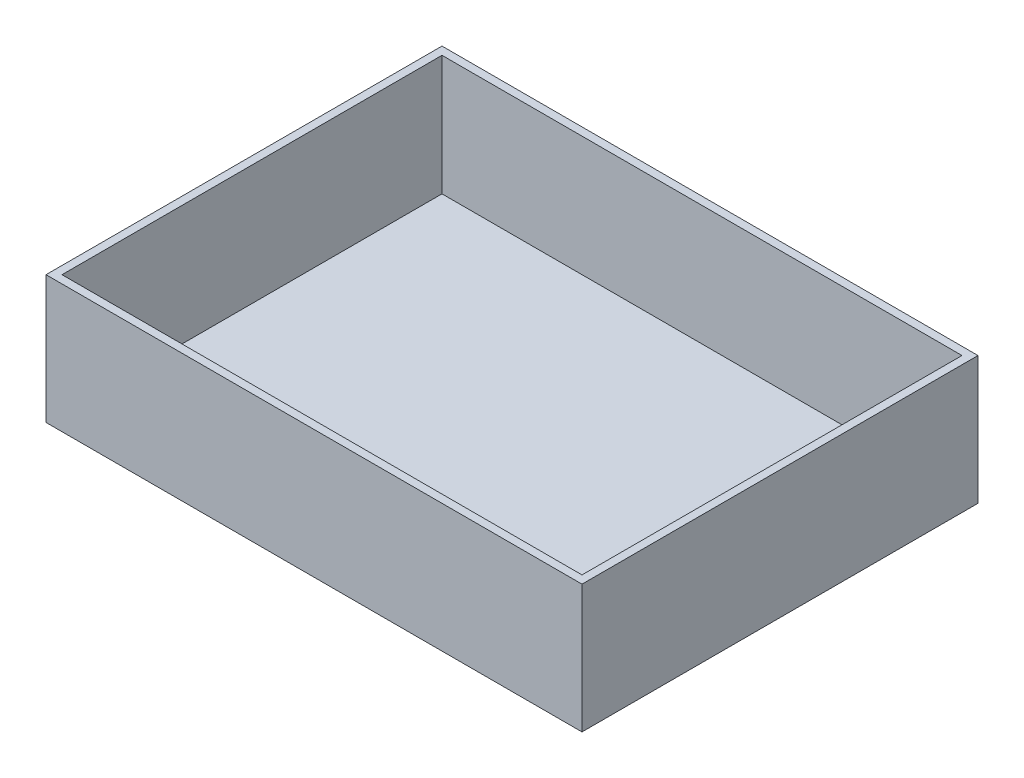
SolidWorks part; units mm, degrees
ref_plane "Alzado" through (0, 0, 0) normal (0, 0, 1) x (1, 0, 0)
ref_plane "Planta" through (0, 0, 0) normal (0, 1, 0) x (1, 0, 0)
ref_plane "Vista lateral" through (0, 0, 0) normal (1, 0, 0) x (0, 0, -1)
sketch "Croquis1" plane through (0, 0, 0) normal (0, 1, 0) x (1, 0, 0)
  line L1 (-130, -95) -> (130, -95)
  line L2 (-130, -95) -> (-130, 95)
  line L3 (-130, 95) -> (130, 95)
  line L4 (130, -95) -> (130, 95)
  line L5 (-130, -95) -> (130, 95) construction
  line L6 (-130, 95) -> (130, -95) construction
  line L7 (-134, -99) -> (134, -99)
  line L8 (-134, -99) -> (-134, 99)
  line L9 (-134, 99) -> (134, 99)
  line L10 (134, -99) -> (134, 99)
  line L11 (-134, -99) -> (134, 99) construction
  line L12 (-134, 99) -> (134, -99) construction
  point P0 (0, 0)
  point P5 (0, 0)
  dimension "D1" = 190
  dimension "D2" = 260
  dimension "D3" = 4
  dimension "D4" = 4
extrude "Saliente-Extruir1" add sketch "Croquis1" along normal blind 60
sketch "Croquis3" plane through (0, 0, 0) normal (0, -1, 0) x (1, 0, 0)
  line L1 (-134, 99) -> (134, 99)
  line L2 (-134, 99) -> (-134, -99)
  line L3 (-134, -99) -> (134, -99)
  line L4 (134, 99) -> (134, -99)
extrude "Saliente-Extruir2" add sketch "Croquis3" along normal blind 4
